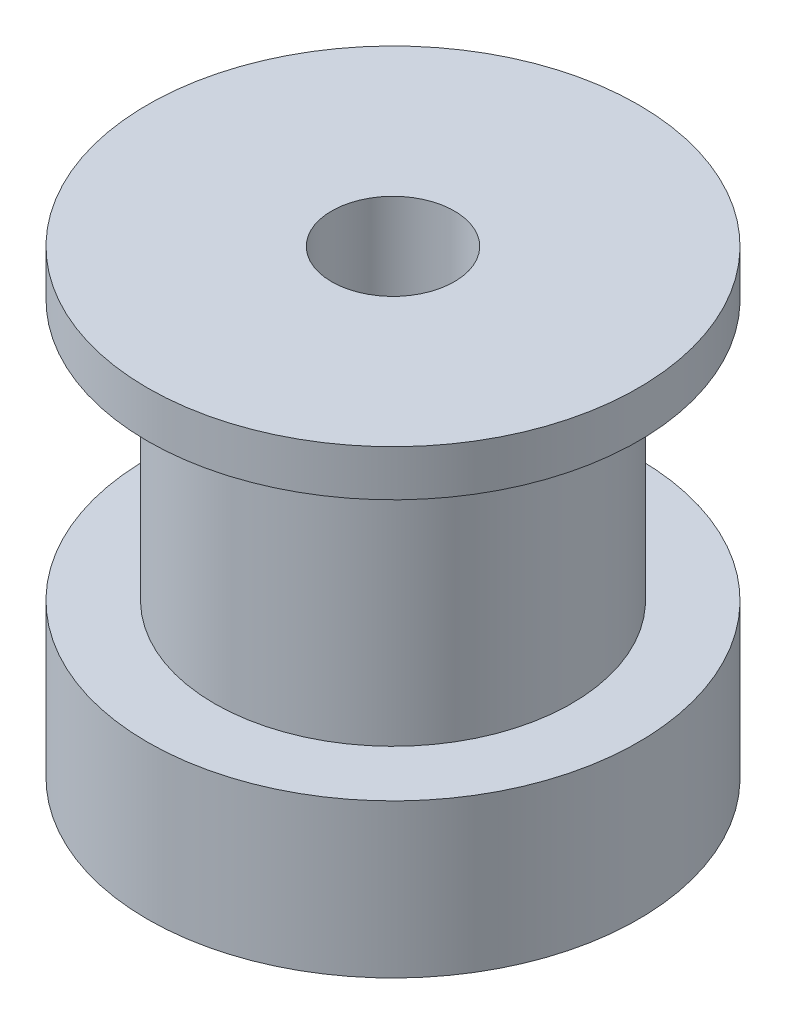
SolidWorks part; units mm, degrees
ref_plane "Alzado" through (0, 0, 0) normal (0, 0, 1) x (1, 0, 0)
ref_plane "Planta" through (0, 0, 0) normal (0, 1, 0) x (1, 0, 0)
ref_plane "Vista lateral" through (0, 0, 0) normal (1, 0, 0) x (0, 0, -1)
sketch "Croquis1" plane through (0, 0, 0) normal (0, 1, 0) x (1, 0, 0)
  circle A0 centre (0, 0) radius 8
  circle A1 centre (0, 0) radius 5.82
  circle A2 centre (0, 0) radius 4.645
  circle A3 centre (0, 0) radius 2
  dimension "D1" = 16
  dimension "D2" = 11.64
  dimension "D3" = 9.29
  dimension "D4" = 4
extrude "Saliente-Extruir1" add sketch "Croquis1" along normal blind 5 contours A0 | A3
extrude "Saliente-Extruir2" add sketch "Croquis1<3>" along normal blind 13.5 contours A1 | A3
sketch "Croquis1<3>" plane through (0, 0, 0) normal (0, 1, 0) x (1, 0, 0) same geometry as "Croquis1"
sketch "Croquis2" plane through (0, 13.5, 0) normal (0, 1, 0) x (1, 0, 0)
  circle A0 centre (0, 0) radius 8
  circle A1 centre (0, 0) radius 8 construction
  circle A2 centre (0, 0) radius 2
  circle A3 centre (0, 0) radius 2 construction
extrude "Saliente-Extruir7" add sketch "Croquis2" along normal blind 1.5
sketch "Croquis3" plane through (0, 0, 0) normal (1, 0, 0) x (0, 0, -1)
  line L0 (0, 8.25) -> (0, -8.25) construction
  line L1 (0, 5) -> (0, 0)
  line L2 (8, 5) -> (-8, 5) construction
  circle A0 centre (0, 2.5) radius 2
  point P9 (0, 2.5)
  dimension "D1" = 4
extrude "Cortar-Extruir1" cut sketch "Croquis3" against normal up to next contours A0
sketch "Croquis4" plane through (0, 0, 0) normal (0, -1, 0) x (1, 0, 0)
  circle A0 centre (0, 0) radius 2.5
  dimension "D1" = 5
extrude "Saliente-Extruir8" [suppressed] add sketch "Croquis4" along normal blind 15
